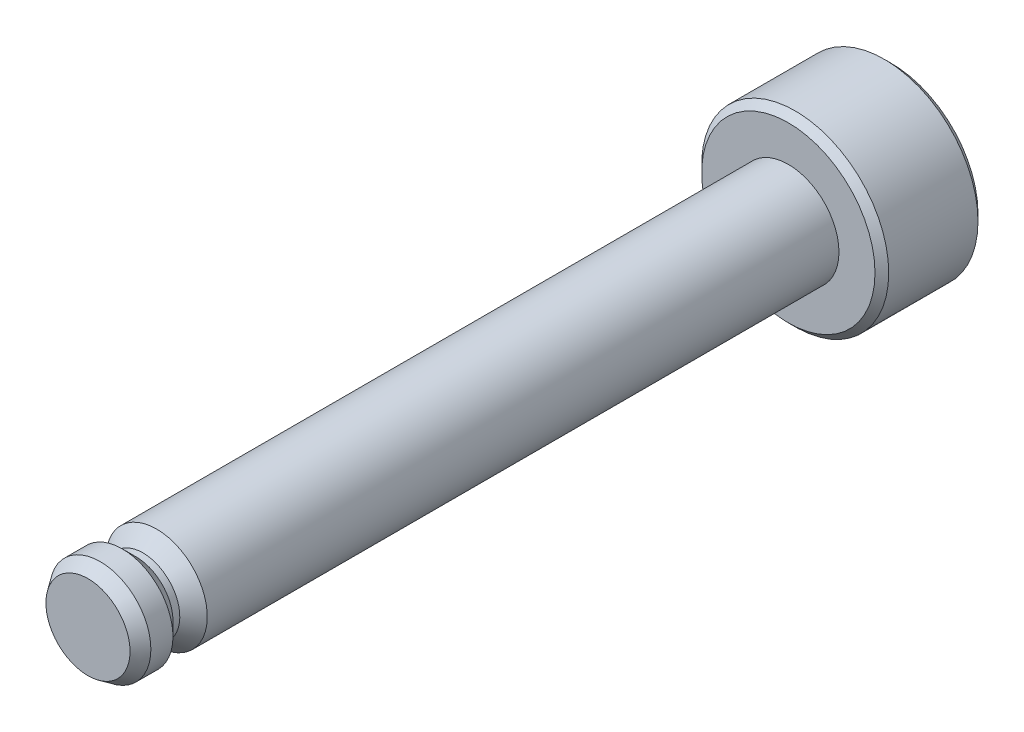
SolidWorks part; units mm, degrees
ref_plane "Front" through (0, 0, 0) normal (0, 0, 1) x (1, 0, 0)
ref_plane "Top" through (0, 0, 0) normal (0, 1, 0) x (1, 0, 0)
ref_plane "Right" through (0, 0, 0) normal (1, 0, 0) x (0, 0, -1)
sketch "Sketch2" plane through (0, 0, 0) normal (0, 0, 1) x (1, 0, 0)
  circle A0 centre (0, 0) radius 1.475
  dimension "D1" = 2.95
extrude "Shaft" add sketch "Sketch2" along normal blind 20.4
sketch "Sketch5" plane through (0, 0, 0) normal (0, 0, 1) x (1, 0, 0)
  circle A0 centre (0, 0) radius 2.725
  dimension "D1" = 5.45
extrude "Head" add sketch "Sketch5" against normal blind 3
chamfer "Chamfer1" distance 0.25 angle 55 1 edges at (1.475, 0, 20.4) first distance on face at (1.475, 0, 20.4)
chamfer "Deburs" distance 0.2 angle 45 2 edges at (2.725, 0, 0) (2.725, 0, -3)
sketch "Sketch6" plane through (0, 0, 0) normal (1, 0, 0) x (0, 0, -1)
  line L0 (0, 0) -> (-18.9, 0) construction
  line L1 (-18.9, 0) -> (-18.9, 1.075) construction
  line L2 (0, 1.475) -> (-20.043, 1.475) construction
  line L3 (-19.4, 1.475) -> (-18.4, 1.475)
  line L4 (-18.4, 1.475) -> (-18.8, 1.075)
  line L5 (-18.8, 1.075) -> (-19, 1.075)
  line L6 (-19, 1.075) -> (-19.4, 1.475)
  line L7 (-18.9, 1.075) -> (-18.9, 1.475) construction
  dimension "D1" = 18.9
  dimension "D2" = 0.4
  dimension "D3" = 1
revolve "e-Clip Notch Long" cut sketch "Sketch6" angle 360 about L0
equation "\"D1@Sketch2\"=\"Plastic Hardware OD@Box Assy.Assembly\""
equation "\"D1\" = \"Countersink Diameter@Box Assy.Assembly\" - .3mm"
equation "\"D1@Head\"=\"Countersink Depth@Box Assy.Assembly\""
equation "\"Length\"= 20mm"
equation "\"D1@Shaft\"=\"Length\"+.4mm"
equation "\"D1@Sketch6\"=\"Length\"-1.1mm"
